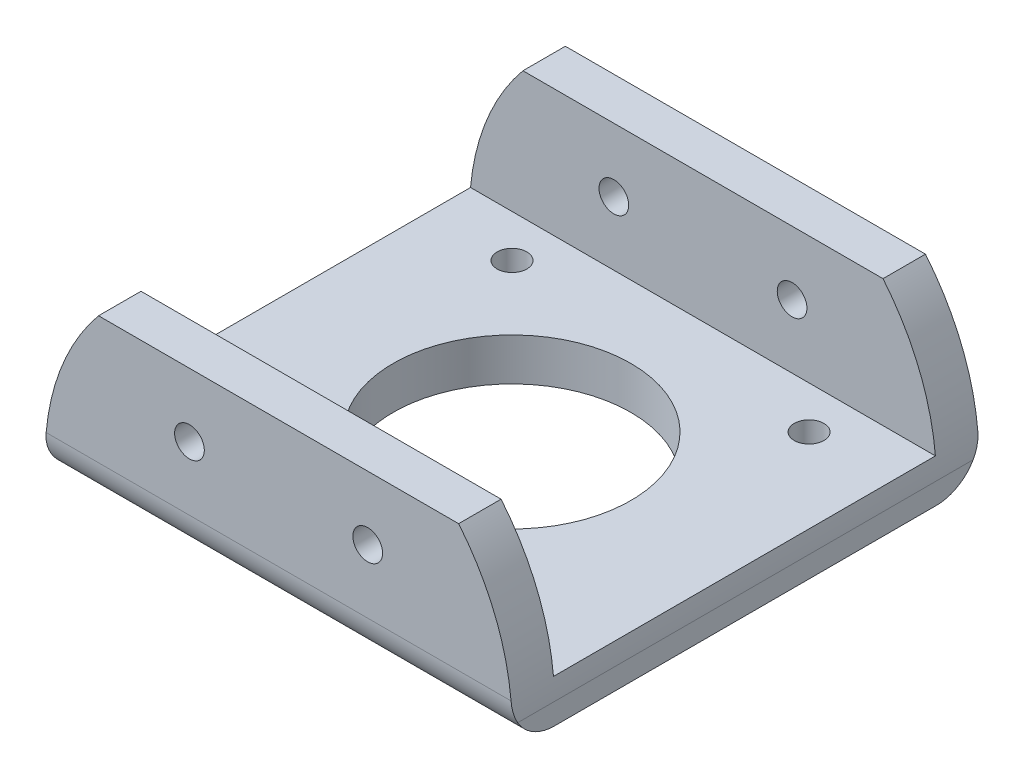
SolidWorks part; units mm, degrees
material "ABS"
ref_plane "Front Plane" through (0, 0, 0) normal (0, 0, 1) x (1, 0, 0)
ref_plane "Top Plane" through (0, 0, 0) normal (0, 1, 0) x (1, 0, 0)
ref_plane "Right Plane" through (0, 0, 0) normal (1, 0, 0) x (0, 0, -1)
sketch "Sketch1" plane through (0, 0, 0) normal (0, 1, 0) x (1, 0, 0)
  line L1 (-27.5, -27.5) -> (27.5, -27.5)
  line L2 (-27.5, -27.5) -> (-27.5, 27.5)
  line L3 (-27.5, 27.5) -> (27.5, 27.5)
  line L4 (27.5, -27.5) -> (27.5, 27.5)
  line L5 (-27.5, -27.5) -> (27.5, 27.5) construction
  line L6 (-27.5, 27.5) -> (27.5, -27.5) construction
  point P0 (0, 0)
  dimension "D1" = 55
  dimension "D2" = 55
extrude "Boss-Extrude1" add sketch "Sketch1" along normal blind 5
sketch "Sketch10" plane through (0, 5, 0) normal (0, 1, 0) x (1, 0, 0)
  line L0 (-27.5, 27.5) -> (-27.5, -27.5) construction
  line L1 (27.5, 27.5) -> (-27.5, 27.5) construction
  line L2 (0, 0) -> (-27.5, 0) construction
  line L3 (0, 0) -> (0, 27.5) construction
  line L4 (0, 0) -> (27.5, 0) construction
  line L5 (0, 0) -> (0, -27.5) construction
  line L6 (0, 0) -> (-27.5, 0) construction
  circle A0 centre (0, 0) radius 14
  circle A1 centre (-17.5, 17.5) radius 1.75
  circle A2 centre (17.5, 17.5) radius 1.75
  circle A3 centre (17.5, -17.5) radius 1.75
  circle A4 centre (-17.5, -17.5) radius 1.75
  point P21 (0, 0)
  point P24 (0, 0)
  dimension "D1" = 28
  dimension "D2" = 3.5
  dimension "D5" = 4
  dimension "D3" = 10
  dimension "D4" = 10
extrude "Cut-Extrude2" cut sketch "Sketch10" against normal up to next contours A0 | A1 | A2 | A3 | A4 region at (0, 5, 0) region at (-17.5, 5, -17.5) region at (17.5, 5, -17.5) region at (17.5, 5, 17.5) region at (-17.5, 5, 17.5)
sketch "Sketch11" plane through (0, 5, 0) normal (0, 1, 0) x (1, 0, 0)
  line L0 (27.5, -27.5) -> (27.5, 27.5) construction
  line L1 (-27.5, 27.5) -> (27.5, 27.5)
  line L2 (-27.5, 27.5) -> (-27.5, 22.5)
  line L3 (-27.5, 22.5) -> (27.5, 22.5)
  line L4 (27.5, 27.5) -> (27.5, 22.5)
  line L5 (27.5, 0) -> (-27.5, 0) construction
  line L6 (-27.5, 27.5) -> (-27.5, -27.5) construction
  line L7 (-27.5, -22.5) -> (27.5, -22.5)
  line L8 (27.5, -27.5) -> (27.5, -22.5)
  line L9 (-27.5, -27.5) -> (27.5, -27.5)
  line L10 (-27.5, -27.5) -> (-27.5, -22.5)
  point P13 (0, 0)
  dimension "D1" = 5
extrude "Boss-Extrude2" add sketch "Sketch11" along normal blind 15
fillet "Fillet1" radius 5 2 edges at (0, 0, -27.5) (0, 0, 27.5)
sketch "Sketch12" plane through (0, 0, -27.5) normal (0, 0, -1) x (-1, 0, 0)
  line L0 (0, 20) -> (0, 5) construction
  line L1 (-27.5, 20) -> (27.5, 20) construction
  line L2 (-27.5, 5) -> (27.5, 5) construction
  line L3 (10.5, 12.5) -> (-10.5, 12.5) construction
  circle A0 centre (-10.5, 12.5) radius 1.75
  circle A1 centre (10.5, 12.5) radius 1.75
  point P13 (0, 12.5)
  dimension "D2" = 3.5
  dimension "D1" = 10.5
extrude "Cut-Extrude3" cut sketch "Sketch12" against normal through all
sketch "Sketch13" plane through (0, 0, 27.5) normal (0, 0, 1) x (1, 0, 0)
  line L0 (-27.5, 2.5) -> (-27.5, 20)
  line L1 (-27.5, 20) -> (-21.2132, 20)
  line L2 (-27.5, 20) -> (27.5, 20) construction
  line L3 (21.2132, 20) -> (27.5, 20)
  line L4 (27.5, 20) -> (27.5, 2.5)
  arc A0 (27.5, 2.5) -> (-27.5, 2.5) centre (0, 2.5) ccw construction
  arc A1 (27.5, 2.5) -> (21.2132, 20) centre (0, 2.5) ccw
  arc A2 (-21.2132, 20) -> (-27.5, 2.5) centre (0, 2.5) ccw
extrude "Cut-Extrude4" cut sketch "Sketch13" against normal through all
